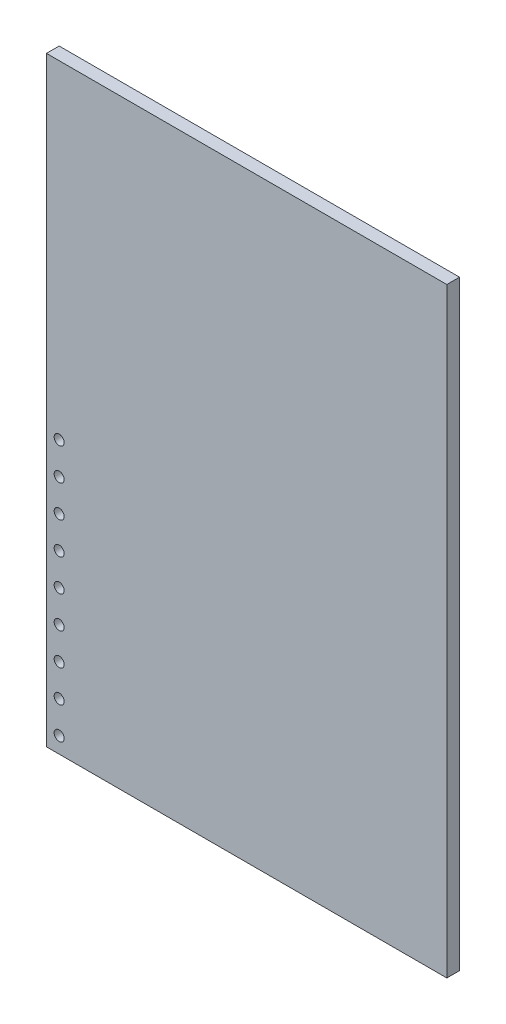
SolidWorks part; units mm, degrees
ref_plane "Front Plane" through (0, 0, 0) normal (0, 0, 1) x (1, 0, 0)
ref_plane "Top Plane" through (0, 0, 0) normal (0, 1, 0) x (1, 0, 0)
ref_plane "Right Plane" through (0, 0, 0) normal (1, 0, 0) x (0, 0, -1)
sketch "Sketch1" plane through (0, 0, 0) normal (0, 1, 0) x (1, 0, 0)
  line L1 (0, 0) -> (100, 0)
  line L2 (0, 0) -> (0, 3.175)
  line L3 (0, 3.175) -> (100, 3.175)
  line L4 (100, 0) -> (100, 3.175)
  dimension "D1" = 100
  dimension "D2" = 3.175
extrude "Boss-Extrude1" add sketch "Sketch1" along normal blind 150
sketch "Sketch2" plane through (0, 0, 0) normal (0, 0, 1) x (1, 0, 0)
  line L0 (6.35, 8) -> (0, 8) construction
  line L5 (0, 0) -> (6.35, 0)
  line L6 (0, 0) -> (0, 16)
  line L8 (6.35, 0) -> (6.35, 16) construction
  line L9 (6.35, 16) -> (0, 16) construction
  line L10 (6.35, 16) -> (6.35, 24) construction
  line L11 (6.35, 24) -> (0, 24) construction
  line L12 (0, 150) -> (0, 0) construction
  line L13 (0, 24) -> (0, 48)
  line L14 (0, 150) -> (0, 0) construction
  line L15 (0, 48) -> (11.1036, 48)
  line L16 (0, 24) -> (0, 32)
  line L17 (0, 32) -> (0, 40)
  line L18 (0, 40) -> (0, 48)
  circle A4 centre (3.175, 4) radius 1.25
  circle A5 centre (3.175, 12) radius 1.25
  circle A6 centre (3.175, 20) radius 1.25
  circle A7 centre (3.175, 44) radius 1.25
  circle A8 centre (3.175, 36) radius 1.25
  circle A9 centre (3.175, 28) radius 1.25
  circle A10 centre (3.175, 68) radius 1.25
  circle A11 centre (3.175, 60) radius 1.25
  circle A12 centre (3.175, 52) radius 1.25
  dimension "D5" = 24
  dimension "D6" = 4
  dimension "D7" = 8
  dimension "D3" = 8
  dimension "D4" = 2.5
  dimension "D1" = 6.35
  dimension "D2" = 8
  dimension "D8" = 3.175
  dimension "D9" = 8
extrude "Cut-Extrude2" cut sketch "Sketch2" against normal blind 5 contours A10
extrude "Cut-Extrude3" cut sketch "Sketch2<14>" against normal blind 5 contours A11
sketch "Sketch2<14>" plane through (0, 0, 0) normal (0, 0, 1) x (1, 0, 0) same geometry as "Sketch2"
extrude "Cut-Extrude4" cut sketch "Sketch2<15>" against normal blind 5 contours A12
sketch "Sketch2<15>" plane through (0, 0, 0) normal (0, 0, 1) x (1, 0, 0) same geometry as "Sketch2"
extrude "Cut-Extrude5" cut sketch "Sketch2<16>" against normal blind 5 contours A7
sketch "Sketch2<16>" plane through (0, 0, 0) normal (0, 0, 1) x (1, 0, 0) same geometry as "Sketch2"
extrude "Cut-Extrude6" cut sketch "Sketch2<17>" against normal blind 5 contours A8
sketch "Sketch2<17>" plane through (0, 0, 0) normal (0, 0, 1) x (1, 0, 0) same geometry as "Sketch2"
extrude "Cut-Extrude7" cut sketch "Sketch2<18>" against normal blind 5 contours A9
sketch "Sketch2<18>" plane through (0, 0, 0) normal (0, 0, 1) x (1, 0, 0) same geometry as "Sketch2"
extrude "Cut-Extrude8" cut sketch "Sketch2<19>" against normal blind 5 contours A6
sketch "Sketch2<19>" plane through (0, 0, 0) normal (0, 0, 1) x (1, 0, 0) same geometry as "Sketch2"
extrude "Cut-Extrude9" cut sketch "Sketch2<20>" against normal blind 5 contours A5
sketch "Sketch2<20>" plane through (0, 0, 0) normal (0, 0, 1) x (1, 0, 0) same geometry as "Sketch2"
extrude "Cut-Extrude10" cut sketch "Sketch2<21>" against normal blind 5 contours A4
sketch "Sketch2<21>" plane through (0, 0, 0) normal (0, 0, 1) x (1, 0, 0) same geometry as "Sketch2"
